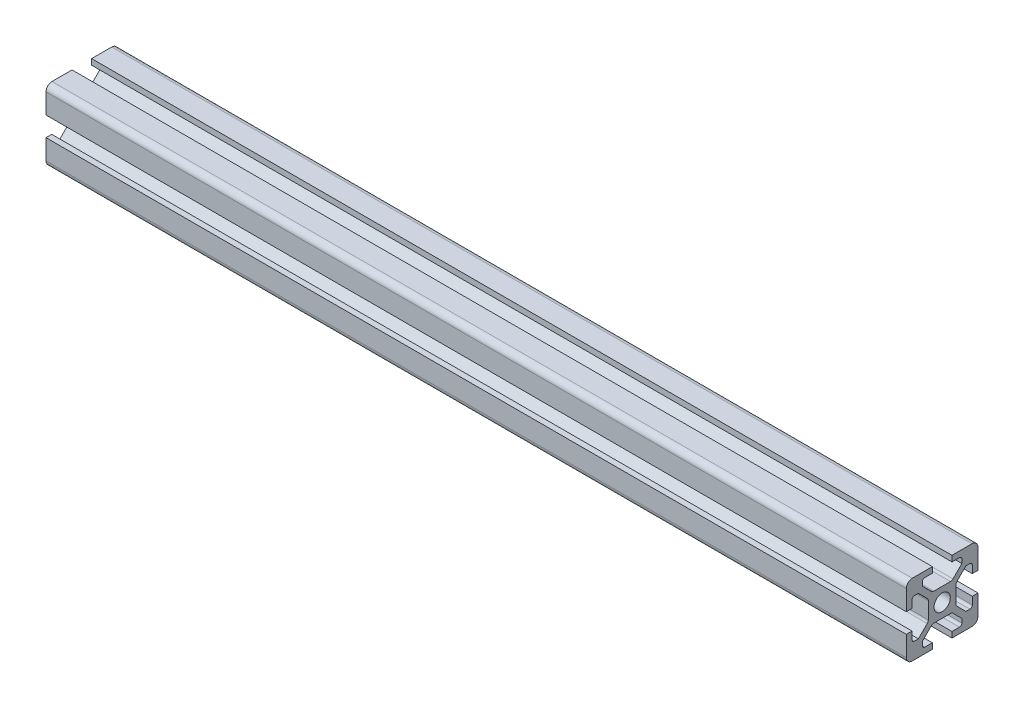
SolidWorks part; units mm, degrees
ref_plane "Front Plane" through (0, 0, 0) normal (0, 0, 1) x (1, 0, 0)
ref_plane "Top Plane" through (0, 0, 0) normal (0, 1, 0) x (1, 0, 0)
ref_plane "Right Plane" through (0, 0, 0) normal (1, 0, 0) x (0, 0, -1)
sketch "Sketch1" plane through (0, 0, 0) normal (1, 0, 0) x (0, 0, -1)
  line L0 (10.9, 0) -> (10.9, 2.4)
  line L1 (0, 0) -> (10.9, 0)
  line L2 (0, 0) -> (0, 10.9)
  line L3 (0, 30) -> (10.9, 30)
  line L4 (30, 0) -> (30, 10.9)
  line L5 (19.1, 0) -> (19.1, 2.4)
  line L6 (0, 10.9) -> (2.4, 10.9)
  line L7 (0, 19.1) -> (2.4, 19.1)
  line L8 (10.9, 30) -> (10.9, 27.6)
  line L9 (19.1, 30) -> (19.1, 27.6)
  line L10 (30, 19.1) -> (27.6, 19.1)
  line L11 (27.6, 10.9) -> (30, 10.9)
  line L12 (24.95, 23.25) -> (27.6, 23.25)
  line L18 (6.75, 2.4) -> (10.9, 2.4)
  line L19 (27.6, 6.75) -> (27.6, 10.9)
  line L20 (2.4, 6.75) -> (2.4, 10.9)
  line L21 (6.75, 27.6) -> (10.9, 27.6)
  line L22 (19.1, 2.4) -> (23.25, 2.4)
  line L23 (27.6, 19.1) -> (27.6, 23.25)
  line L24 (2.4, 19.1) -> (2.4, 23.25)
  line L25 (19.1, 27.6) -> (23.25, 27.6)
  line L26 (19.1, 20.8) -> (10.9, 20.8)
  line L29 (5.05, 6.75) -> (2.4, 6.75)
  line L31 (2.4, 23.25) -> (5.05, 23.25)
  line L34 (6.75, 24.95) -> (6.75, 27.6)
  line L40 (23.25, 2.4) -> (23.25, 5.05)
  line L43 (9.2, 10.9) -> (9.2, 19.1)
  line L44 (19.1, 9.2) -> (10.9, 9.2)
  line L45 (20.8, 10.9) -> (20.8, 19.1)
  line L46 (24.95, 6.75) -> (20.8, 10.9)
  line L47 (19.1, 9.2) -> (23.25, 5.05)
  line L48 (20.8, 19.1) -> (24.95, 23.25)
  line L49 (10.9, 9.2) -> (6.75, 5.05)
  line L50 (5.05, 6.75) -> (9.2, 10.9)
  line L51 (19.1, 20.8) -> (23.25, 24.95)
  line L52 (6.75, 24.95) -> (10.9, 20.8)
  line L53 (5.05, 23.25) -> (9.2, 19.1)
  line L54 (19.1, 30) -> (30, 30)
  line L55 (30, 19.1) -> (30, 30)
  line L56 (19.1, 0) -> (30, 0)
  line L57 (0, 19.1) -> (0, 30)
  line L58 (6.75, 5.05) -> (6.75, 2.4)
  line L59 (24.95, 6.75) -> (27.6, 6.75)
  line L60 (23.25, 27.6) -> (23.25, 24.95)
  circle A0 centre (15, 15) radius 3.4
  point P5 (10.9, 0)
  point P6 (19.1, 0)
  point P7 (0, 10.9)
  point P8 (0, 19.1)
  point P9 (30, 19.1)
  point P10 (30, 10.9)
  point P11 (19.1, 30)
  point P12 (10.9, 30)
  point P59 (15, 20.8)
  point P61 (9.2, 15)
  point P62 (15, 9.2)
  point P65 (20.8, 15)
  point P67 (24.95, 6.75)
  point P70 (15, 20.8)
  point P73 (9.2, 15)
  point P76 (15, 9.2)
  point P79 (20.8, 15)
  point P80 (23.25, 5.05)
  point P81 (24.95, 23.25)
  point P82 (6.75, 5.05)
  point P84 (5.05, 6.75)
  point P88 (23.25, 24.95)
  point P90 (6.75, 24.95)
  point P92 (5.05, 23.25)
extrude "Boss-Extrude2" add sketch "Sketch1" along normal blind 100
fillet "Fillet5" radius 2.5 4 edges at (50, 0, -30) (50, 30, -30) (50, 0, 0) (50, 30, 0)
fillet "Fillet6" radius 1.5 6 edges at (50, 19.1, -20.8) (50, 10.9, -20.8) (50, 9.2, -10.9) (50, 9.2, -19.1) (50, 10.9, -9.2) (50, 19.1, -9.2)
fillet "Fillet7" radius 1.5 2 edges at (50, 20.8, -19.1) (50, 20.8, -10.9)
fillet "Fillet8" radius 1 8 edges at (50, 23.25, -2.4) (50, 27.6, -6.75) (50, 27.6, -23.25) (50, 23.25, -27.6) (50, 6.75, -27.6) (50, 2.4, -23.25) (50, 2.4, -6.75) (50, 6.75, -2.4)
sketch "Sketch3" plane through (0, 0, 0) normal (1, 0, 0) x (0, 0, -1)
  line L0 (10.9, 27.6) -> (10.9, 30) construction
  line L1 (7.75, 27.6) -> (10.9, 27.6) construction
  line L2 (6.75, 24.95) -> (6.75, 26.6) construction
  line L3 (10.4607, 21.2393) -> (6.75, 24.95) construction
  line L4 (18.4787, 20.8) -> (11.5213, 20.8) construction
  line L5 (23.25, 24.95) -> (19.5393, 21.2393) construction
  line L6 (23.25, 26.6) -> (23.25, 24.95) construction
  line L7 (19.1, 27.6) -> (22.25, 27.6) construction
  line L8 (19.1, 30) -> (19.1, 27.6) construction
  line L9 (27.5, 30) -> (19.1, 30) construction
  line L10 (30, 19.1) -> (30, 27.5) construction
  line L11 (27.6, 19.1) -> (30, 19.1) construction
  line L12 (27.6, 22.25) -> (27.6, 19.1) construction
  line L13 (24.95, 23.25) -> (26.6, 23.25) construction
  line L14 (21.2393, 19.5393) -> (24.95, 23.25) construction
  line L15 (20.8, 11.5213) -> (20.8, 18.4787) construction
  line L16 (24.95, 6.75) -> (21.2393, 10.4607) construction
  line L17 (26.6, 6.75) -> (24.95, 6.75) construction
  line L18 (27.6, 10.9) -> (27.6, 7.75) construction
  line L19 (30, 10.9) -> (27.6, 10.9) construction
  line L20 (30, 2.5) -> (30, 10.9) construction
  line L21 (19.1, 0) -> (27.5, 0) construction
  line L22 (19.1, 2.4) -> (19.1, 0) construction
  line L23 (22.25, 2.4) -> (19.1, 2.4) construction
  line L24 (23.25, 5.05) -> (23.25, 3.4) construction
  line L25 (19.5393, 8.7607) -> (23.25, 5.05) construction
  line L26 (11.5213, 9.2) -> (18.4787, 9.2) construction
  line L27 (6.75, 5.05) -> (10.4607, 8.7607) construction
  line L28 (6.75, 3.4) -> (6.75, 5.05) construction
  line L29 (10.9, 2.4) -> (7.75, 2.4) construction
  line L30 (10.9, 0) -> (10.9, 2.4) construction
  line L31 (2.5, 0) -> (10.9, 0) construction
  line L32 (0, 10.9) -> (0, 2.5) construction
  line L33 (2.4, 10.9) -> (0, 10.9) construction
  line L34 (2.4, 7.75) -> (2.4, 10.9) construction
  line L35 (5.05, 6.75) -> (3.4, 6.75) construction
  line L36 (8.7607, 10.4607) -> (5.05, 6.75) construction
  line L37 (9.2, 18.4787) -> (9.2, 11.5213) construction
  line L38 (5.05, 23.25) -> (8.7607, 19.5393) construction
  line L39 (3.4, 23.25) -> (5.05, 23.25) construction
  line L40 (2.4, 19.1) -> (2.4, 22.25) construction
  line L41 (0, 19.1) -> (2.4, 19.1) construction
  line L42 (0, 27.5) -> (0, 19.1) construction
  line L43 (10.9, 30) -> (2.5, 30) construction
  line L44 (10.9, 27.6) -> (10.9, 30)
  line L45 (7.75, 27.6) -> (10.9, 27.6)
  line L46 (6.75, 24.95) -> (6.75, 26.6)
  line L47 (10.4607, 21.2393) -> (6.75, 24.95)
  line L48 (18.4787, 20.8) -> (11.5213, 20.8)
  line L49 (23.25, 24.95) -> (19.5393, 21.2393)
  line L50 (23.25, 26.6) -> (23.25, 24.95)
  line L51 (19.1, 27.6) -> (22.25, 27.6)
  line L52 (19.1, 30) -> (19.1, 27.6)
  line L53 (27.5, 30) -> (19.1, 30)
  line L54 (30, 19.1) -> (30, 27.5)
  line L55 (27.6, 19.1) -> (30, 19.1)
  line L56 (27.6, 22.25) -> (27.6, 19.1)
  line L57 (24.95, 23.25) -> (26.6, 23.25)
  line L58 (21.2393, 19.5393) -> (24.95, 23.25)
  line L59 (20.8, 11.5213) -> (20.8, 18.4787)
  line L60 (24.95, 6.75) -> (21.2393, 10.4607)
  line L61 (26.6, 6.75) -> (24.95, 6.75)
  line L62 (27.6, 10.9) -> (27.6, 7.75)
  line L63 (30, 10.9) -> (27.6, 10.9)
  line L64 (30, 2.5) -> (30, 10.9)
  line L65 (19.1, 0) -> (27.5, 0)
  line L66 (19.1, 2.4) -> (19.1, 0)
  line L67 (22.25, 2.4) -> (19.1, 2.4)
  line L68 (23.25, 5.05) -> (23.25, 3.4)
  line L69 (19.5393, 8.7607) -> (23.25, 5.05)
  line L70 (11.5213, 9.2) -> (18.4787, 9.2)
  line L71 (6.75, 5.05) -> (10.4607, 8.7607)
  line L72 (6.75, 3.4) -> (6.75, 5.05)
  line L73 (10.9, 2.4) -> (7.75, 2.4)
  line L74 (10.9, 0) -> (10.9, 2.4)
  line L75 (2.5, 0) -> (10.9, 0)
  line L76 (0, 10.9) -> (0, 2.5)
  line L77 (2.4, 10.9) -> (0, 10.9)
  line L78 (2.4, 7.75) -> (2.4, 10.9)
  line L79 (5.05, 6.75) -> (3.4, 6.75)
  line L80 (8.7607, 10.4607) -> (5.05, 6.75)
  line L81 (9.2, 18.4787) -> (9.2, 11.5213)
  line L82 (5.05, 23.25) -> (8.7607, 19.5393)
  line L83 (3.4, 23.25) -> (5.05, 23.25)
  line L84 (2.4, 19.1) -> (2.4, 22.25)
  line L85 (0, 19.1) -> (2.4, 19.1)
  line L86 (0, 27.5) -> (0, 19.1)
  line L87 (10.9, 30) -> (2.5, 30)
  circle A0 centre (15, 15) radius 3.4 construction
  arc A1 (7.75, 27.6) -> (6.75, 26.6) centre (7.75, 26.6) ccw construction
  arc A2 (10.4607, 21.2393) -> (11.5213, 20.8) centre (11.5213, 22.3) ccw construction
  arc A3 (18.4787, 20.8) -> (19.5393, 21.2393) centre (18.4787, 22.3) ccw construction
  arc A4 (23.25, 26.6) -> (22.25, 27.6) centre (22.25, 26.6) ccw construction
  arc A5 (30, 27.5) -> (27.5, 30) centre (27.5, 27.5) ccw construction
  arc A6 (27.6, 22.25) -> (26.6, 23.25) centre (26.6, 22.25) ccw construction
  arc A7 (21.2393, 19.5393) -> (20.8, 18.4787) centre (22.3, 18.4787) ccw construction
  arc A8 (20.8, 11.5213) -> (21.2393, 10.4607) centre (22.3, 11.5213) ccw construction
  arc A9 (26.6, 6.75) -> (27.6, 7.75) centre (26.6, 7.75) ccw construction
  arc A10 (27.5, 0) -> (30, 2.5) centre (27.5, 2.5) ccw construction
  arc A11 (22.25, 2.4) -> (23.25, 3.4) centre (22.25, 3.4) ccw construction
  arc A12 (19.5393, 8.7607) -> (18.4787, 9.2) centre (18.4787, 7.7) ccw construction
  arc A13 (11.5213, 9.2) -> (10.4607, 8.7607) centre (11.5213, 7.7) ccw construction
  arc A14 (6.75, 3.4) -> (7.75, 2.4) centre (7.75, 3.4) ccw construction
  arc A15 (0, 2.5) -> (2.5, 0) centre (2.5, 2.5) ccw construction
  arc A16 (2.4, 7.75) -> (3.4, 6.75) centre (3.4, 7.75) ccw construction
  arc A17 (9.2, 18.4787) -> (8.7607, 19.5393) centre (7.7, 18.4787) ccw construction
  arc A18 (8.7607, 10.4607) -> (9.2, 11.5213) centre (7.7, 11.5213) ccw construction
  arc A19 (3.4, 23.25) -> (2.4, 22.25) centre (3.4, 22.25) ccw construction
  arc A20 (2.5, 30) -> (0, 27.5) centre (2.5, 27.5) ccw construction
  circle A21 centre (15, 15) radius 3.4
  arc A22 (7.75, 27.6) -> (6.75, 26.6) centre (7.75, 26.6) ccw
  arc A23 (10.4607, 21.2393) -> (11.5213, 20.8) centre (11.5213, 22.3) ccw
  arc A24 (18.4787, 20.8) -> (19.5393, 21.2393) centre (18.4787, 22.3) ccw
  arc A25 (23.25, 26.6) -> (22.25, 27.6) centre (22.25, 26.6) ccw
  arc A26 (30, 27.5) -> (27.5, 30) centre (27.5, 27.5) ccw
  arc A27 (27.6, 22.25) -> (26.6, 23.25) centre (26.6, 22.25) ccw
  arc A28 (21.2393, 19.5393) -> (20.8, 18.4787) centre (22.3, 18.4787) ccw
  arc A29 (20.8, 11.5213) -> (21.2393, 10.4607) centre (22.3, 11.5213) ccw
  arc A30 (26.6, 6.75) -> (27.6, 7.75) centre (26.6, 7.75) ccw
  arc A31 (27.5, 0) -> (30, 2.5) centre (27.5, 2.5) ccw
  arc A32 (22.25, 2.4) -> (23.25, 3.4) centre (22.25, 3.4) ccw
  arc A33 (19.5393, 8.7607) -> (18.4787, 9.2) centre (18.4787, 7.7) ccw
  arc A34 (11.5213, 9.2) -> (10.4607, 8.7607) centre (11.5213, 7.7) ccw
  arc A35 (6.75, 3.4) -> (7.75, 2.4) centre (7.75, 3.4) ccw
  arc A36 (0, 2.5) -> (2.5, 0) centre (2.5, 2.5) ccw
  arc A37 (2.4, 7.75) -> (3.4, 6.75) centre (3.4, 7.75) ccw
  arc A38 (9.2, 18.4787) -> (8.7607, 19.5393) centre (7.7, 18.4787) ccw
  arc A39 (8.7607, 10.4607) -> (9.2, 11.5213) centre (7.7, 11.5213) ccw
  arc A40 (3.4, 23.25) -> (2.4, 22.25) centre (3.4, 22.25) ccw
  arc A41 (2.5, 30) -> (0, 27.5) centre (2.5, 27.5) ccw
extrude "Boss-Extrude3" add sketch "Sketch3" against normal blind 140
sketch "Sketch7" plane through (-140, 0, 0) normal (-1, 0, 0) x (0, 0, 1)
  line L0 (-2.4, 10.9) -> (0, 10.9) construction
  line L1 (0, 10.9) -> (0, 2.5) construction
  line L2 (-2.5, 0) -> (-10.9, 0) construction
  line L3 (-10.9, 0) -> (-10.9, 2.4) construction
  line L4 (-10.9, 2.4) -> (-7.75, 2.4) construction
  line L5 (-2.4, 7.75) -> (-2.4, 10.9) construction
  line L6 (-5.05, 6.75) -> (-3.4, 6.75) construction
  line L7 (-6.75, 3.4) -> (-6.75, 5.05) construction
  line L8 (-6.75, 5.05) -> (-10.4607, 8.7607) construction
  line L9 (-8.7607, 10.4607) -> (-5.05, 6.75) construction
  line L10 (-9.2, 18.4787) -> (-9.2, 11.5213) construction
  line L11 (-11.5213, 9.2) -> (-18.4787, 9.2) construction
  line L12 (-5.05, 23.25) -> (-8.7607, 19.5393) construction
  line L13 (-19.5393, 8.7607) -> (-23.25, 5.05) construction
  line L14 (-23.25, 5.05) -> (-23.25, 3.4) construction
  line L15 (-22.25, 2.4) -> (-19.1, 2.4) construction
  line L16 (-3.4, 23.25) -> (-5.05, 23.25) construction
  line L17 (-2.4, 19.1) -> (-2.4, 22.25) construction
  line L18 (0, 19.1) -> (-2.4, 19.1) construction
  line L19 (0, 27.5) -> (0, 19.1) construction
  line L20 (-19.1, 2.4) -> (-19.1, 0) construction
  line L21 (-19.1, 0) -> (-27.5, 0) construction
  line L22 (-10.9, 30) -> (-2.5, 30) construction
  line L23 (-30, 2.5) -> (-30, 10.9) construction
  line L24 (-30, 10.9) -> (-27.6, 10.9) construction
  line L25 (-27.6, 10.9) -> (-27.6, 7.75) construction
  line L26 (-10.9, 27.6) -> (-10.9, 30) construction
  line L27 (-7.75, 27.6) -> (-10.9, 27.6) construction
  line L28 (-6.75, 24.95) -> (-6.75, 26.6) construction
  line L29 (-26.6, 6.75) -> (-24.95, 6.75) construction
  line L30 (-24.95, 6.75) -> (-21.2393, 10.4607) construction
  line L31 (-10.4607, 21.2393) -> (-6.75, 24.95) construction
  line L32 (-18.4787, 20.8) -> (-11.5213, 20.8) construction
  line L33 (-20.8, 11.5213) -> (-20.8, 18.4787) construction
  line L34 (-23.25, 24.95) -> (-19.5393, 21.2393) construction
  line L35 (-21.2393, 19.5393) -> (-24.95, 23.25) construction
  line L36 (-19.1, 30) -> (-19.1, 27.6) construction
  line L37 (-19.1, 27.6) -> (-22.25, 27.6) construction
  line L38 (-23.25, 26.6) -> (-23.25, 24.95) construction
  line L39 (-27.5, 30) -> (-19.1, 30) construction
  line L40 (-24.95, 23.25) -> (-26.6, 23.25) construction
  line L41 (-27.6, 19.1) -> (-30, 19.1) construction
  line L42 (-27.6, 22.25) -> (-27.6, 19.1) construction
  line L43 (-30, 19.1) -> (-30, 27.5) construction
  line L44 (-2.4, 10.9) -> (0, 10.9)
  line L45 (0, 10.9) -> (0, 2.5)
  line L46 (-2.5, 0) -> (-10.9, 0)
  line L47 (-10.9, 0) -> (-10.9, 2.4)
  line L48 (-10.9, 2.4) -> (-7.75, 2.4)
  line L49 (-2.4, 7.75) -> (-2.4, 10.9)
  line L50 (-5.05, 6.75) -> (-3.4, 6.75)
  line L51 (-6.75, 3.4) -> (-6.75, 5.05)
  line L52 (-6.75, 5.05) -> (-10.4607, 8.7607)
  line L53 (-8.7607, 10.4607) -> (-5.05, 6.75)
  line L54 (-9.2, 18.4787) -> (-9.2, 11.5213)
  line L55 (-11.5213, 9.2) -> (-18.4787, 9.2)
  line L56 (-5.05, 23.25) -> (-8.7607, 19.5393)
  line L57 (-19.5393, 8.7607) -> (-23.25, 5.05)
  line L58 (-23.25, 5.05) -> (-23.25, 3.4)
  line L59 (-22.25, 2.4) -> (-19.1, 2.4)
  line L60 (-3.4, 23.25) -> (-5.05, 23.25)
  line L61 (-2.4, 19.1) -> (-2.4, 22.25)
  line L62 (0, 19.1) -> (-2.4, 19.1)
  line L63 (0, 27.5) -> (0, 19.1)
  line L64 (-19.1, 2.4) -> (-19.1, 0)
  line L65 (-19.1, 0) -> (-27.5, 0)
  line L66 (-10.9, 30) -> (-2.5, 30)
  line L67 (-30, 2.5) -> (-30, 10.9)
  line L68 (-30, 10.9) -> (-27.6, 10.9)
  line L69 (-27.6, 10.9) -> (-27.6, 7.75)
  line L70 (-10.9, 27.6) -> (-10.9, 30)
  line L71 (-7.75, 27.6) -> (-10.9, 27.6)
  line L72 (-6.75, 24.95) -> (-6.75, 26.6)
  line L73 (-26.6, 6.75) -> (-24.95, 6.75)
  line L74 (-24.95, 6.75) -> (-21.2393, 10.4607)
  line L75 (-10.4607, 21.2393) -> (-6.75, 24.95)
  line L76 (-18.4787, 20.8) -> (-11.5213, 20.8)
  line L77 (-20.8, 11.5213) -> (-20.8, 18.4787)
  line L78 (-23.25, 24.95) -> (-19.5393, 21.2393)
  line L79 (-21.2393, 19.5393) -> (-24.95, 23.25)
  line L80 (-19.1, 30) -> (-19.1, 27.6)
  line L81 (-19.1, 27.6) -> (-22.25, 27.6)
  line L82 (-23.25, 26.6) -> (-23.25, 24.95)
  line L83 (-27.5, 30) -> (-19.1, 30)
  line L84 (-24.95, 23.25) -> (-26.6, 23.25)
  line L85 (-27.6, 19.1) -> (-30, 19.1)
  line L86 (-27.6, 22.25) -> (-27.6, 19.1)
  line L87 (-30, 19.1) -> (-30, 27.5)
  arc A0 (-2.5, 0) -> (0, 2.5) centre (-2.5, 2.5) ccw construction
  arc A1 (-3.4, 6.75) -> (-2.4, 7.75) centre (-3.4, 7.75) ccw construction
  arc A2 (-7.75, 2.4) -> (-6.75, 3.4) centre (-7.75, 3.4) ccw construction
  arc A3 (-10.4607, 8.7607) -> (-11.5213, 9.2) centre (-11.5213, 7.7) ccw construction
  arc A4 (-9.2, 11.5213) -> (-8.7607, 10.4607) centre (-7.7, 11.5213) ccw construction
  arc A5 (-8.7607, 19.5393) -> (-9.2, 18.4787) centre (-7.7, 18.4787) ccw construction
  arc A6 (-18.4787, 9.2) -> (-19.5393, 8.7607) centre (-18.4787, 7.7) ccw construction
  arc A7 (-23.25, 3.4) -> (-22.25, 2.4) centre (-22.25, 3.4) ccw construction
  arc A8 (-2.4, 22.25) -> (-3.4, 23.25) centre (-3.4, 22.25) ccw construction
  arc A9 (-30, 2.5) -> (-27.5, 0) centre (-27.5, 2.5) ccw construction
  arc A10 (0, 27.5) -> (-2.5, 30) centre (-2.5, 27.5) ccw construction
  arc A11 (-27.6, 7.75) -> (-26.6, 6.75) centre (-26.6, 7.75) ccw construction
  arc A12 (-6.75, 26.6) -> (-7.75, 27.6) centre (-7.75, 26.6) ccw construction
  arc A13 (-21.2393, 10.4607) -> (-20.8, 11.5213) centre (-22.3, 11.5213) ccw construction
  arc A14 (-11.5213, 20.8) -> (-10.4607, 21.2393) centre (-11.5213, 22.3) ccw construction
  circle A15 centre (-15, 15) radius 3.4 construction
  arc A16 (-20.8, 18.4787) -> (-21.2393, 19.5393) centre (-22.3, 18.4787) ccw construction
  arc A17 (-19.5393, 21.2393) -> (-18.4787, 20.8) centre (-18.4787, 22.3) ccw construction
  arc A18 (-22.25, 27.6) -> (-23.25, 26.6) centre (-22.25, 26.6) ccw construction
  arc A19 (-27.5, 30) -> (-30, 27.5) centre (-27.5, 27.5) ccw construction
  arc A20 (-26.6, 23.25) -> (-27.6, 22.25) centre (-26.6, 22.25) ccw construction
  arc A21 (-2.5, 0) -> (0, 2.5) centre (-2.5, 2.5) ccw
  arc A22 (-3.4, 6.75) -> (-2.4, 7.75) centre (-3.4, 7.75) ccw
  arc A23 (-7.75, 2.4) -> (-6.75, 3.4) centre (-7.75, 3.4) ccw
  arc A24 (-10.4607, 8.7607) -> (-11.5213, 9.2) centre (-11.5213, 7.7) ccw
  arc A25 (-9.2, 11.5213) -> (-8.7607, 10.4607) centre (-7.7, 11.5213) ccw
  arc A26 (-8.7607, 19.5393) -> (-9.2, 18.4787) centre (-7.7, 18.4787) ccw
  arc A27 (-18.4787, 9.2) -> (-19.5393, 8.7607) centre (-18.4787, 7.7) ccw
  arc A28 (-23.25, 3.4) -> (-22.25, 2.4) centre (-22.25, 3.4) ccw
  arc A29 (-2.4, 22.25) -> (-3.4, 23.25) centre (-3.4, 22.25) ccw
  arc A30 (-30, 2.5) -> (-27.5, 0) centre (-27.5, 2.5) ccw
  arc A31 (0, 27.5) -> (-2.5, 30) centre (-2.5, 27.5) ccw
  arc A32 (-27.6, 7.75) -> (-26.6, 6.75) centre (-26.6, 7.75) ccw
  arc A33 (-6.75, 26.6) -> (-7.75, 27.6) centre (-7.75, 26.6) ccw
  arc A34 (-21.2393, 10.4607) -> (-20.8, 11.5213) centre (-22.3, 11.5213) ccw
  arc A35 (-11.5213, 20.8) -> (-10.4607, 21.2393) centre (-11.5213, 22.3) ccw
  circle A36 centre (-15, 15) radius 3.4
  arc A37 (-20.8, 18.4787) -> (-21.2393, 19.5393) centre (-22.3, 18.4787) ccw
  arc A38 (-19.5393, 21.2393) -> (-18.4787, 20.8) centre (-18.4787, 22.3) ccw
  arc A39 (-22.25, 27.6) -> (-23.25, 26.6) centre (-22.25, 26.6) ccw
  arc A40 (-27.5, 30) -> (-30, 27.5) centre (-27.5, 27.5) ccw
  arc A41 (-26.6, 23.25) -> (-27.6, 22.25) centre (-26.6, 22.25) ccw
extrude "Boss-Extrude4" add sketch "Sketch7" along normal blind 120
